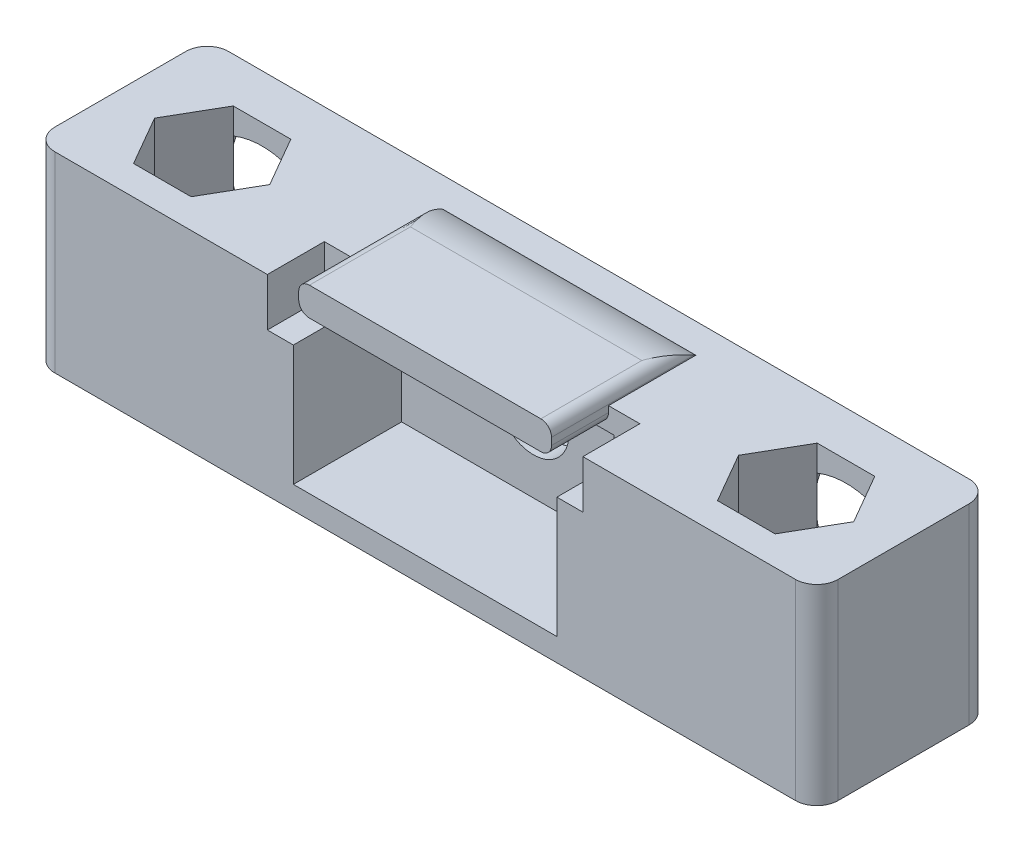
SolidWorks part; units mm, degrees
ref_plane "Front Plane" through (0, 0, 0) normal (0, 0, 1) x (1, 0, 0)
ref_plane "Top Plane" through (0, 0, 0) normal (0, 1, 0) x (1, 0, 0)
ref_plane "Right Plane" through (0, 0, 0) normal (1, 0, 0) x (0, 0, -1)
sketch "Sketch2" plane through (0, 0, 0) normal (0, 0, 1) x (1, 0, 0)
  line L1 (0, 0) -> (55, 0)
  line L2 (0, 0) -> (0, 13.45)
  line L3 (0, 13.45) -> (55, 13.45)
  line L4 (55, 0) -> (55, 13.45)
  dimension "D1" = 13.45
  dimension "D2" = 55
extrude "Boss-Extrude1" add sketch "Sketch2" along normal blind 12.2
sketch "Sketch3" plane through (0, 0, 12.2) normal (0, 0, 1) x (1, 0, 0)
  line L0 (0, 0) -> (55, 0) construction
  line L1 (18.25, 11.85) -> (36.75, 11.85)
  line L2 (18.25, 11.85) -> (18.25, 1.6)
  line L3 (18.25, 1.6) -> (36.75, 1.6)
  line L4 (36.75, 11.85) -> (36.75, 1.6)
  line L5 (27.5, 26.9) -> (27.5, 0) construction
  line L7 (27.5, 0) -> (27.5, -19.69) construction
  point P6 (27.5, 11.85)
  point P9 (27.5, 13.45)
  dimension "D1" = 1.6
  dimension "D2" = 18.5
  dimension "D3" = 11.85
extrude "Cut-Extrude1" cut sketch "Sketch3" against normal blind 7.6
sketch "Sketch5" plane through (0, 0, 12.2) normal (0, 0, 1) x (1, 0, 0)
  line L0 (27.5, 13.45) -> (27.5, -4.8209) construction
  line L1 (55, 13.45) -> (0, 13.45) construction
  line L3 (16.425, 13.45) -> (38.575, 13.45)
  line L4 (16.425, 13.45) -> (16.425, 11.85)
  line L5 (16.425, 11.85) -> (38.575, 11.85)
  line L6 (38.575, 13.45) -> (38.575, 11.85)
  point P1 (27.5, 13.45)
  dimension "D1" = 1.6
  dimension "D2" = 22.15
extrude "Cut-Extrude2" cut sketch "Sketch5" against normal blind 4
sketch "Sketch6" plane through (0, 0, 12.2) normal (0, 0, 1) x (1, 0, 0)
  line L0 (27.5, 0) -> (27.5, 20.3445) construction
  line L1 (0, 0) -> (55, 0) construction
  line L2 (36.75, 11.85) -> (18.25, 11.85) construction
  line L3 (18.625, 12.275) -> (36.375, 12.275)
  line L4 (18.625, 12.275) -> (18.625, 14.275)
  line L5 (18.625, 14.275) -> (36.375, 14.275)
  line L6 (36.375, 12.275) -> (36.375, 14.275)
  point P10 (27.5, 14.275)
  dimension "D1" = 0.425
  dimension "D2" = 17.75
  dimension "D3" = 2
extrude "Boss-Extrude2" add sketch "Sketch6" against normal blind 8.7
sketch "Sketch7" plane through (0, 0, 12.2) normal (0, 0, 1) x (1, 0, 0)
  line L0 (36.75, 1.6) -> (36.75, 11.85) construction
  line L1 (38.575, 13.45) -> (36.75, 13.45)
  line L2 (38.575, 13.45) -> (38.575, 10.075)
  line L3 (38.575, 10.075) -> (36.75, 10.075)
  line L4 (36.75, 13.45) -> (36.75, 10.075)
  line L5 (18.25, 11.85) -> (18.25, 1.6) construction
  line L6 (16.425, 13.45) -> (18.25, 13.45)
  line L7 (16.425, 13.45) -> (16.425, 10.075)
  line L8 (16.425, 10.075) -> (18.25, 10.075)
  line L9 (18.25, 13.45) -> (18.25, 10.075)
  dimension "D1" = 3.375
  dimension "D2" = 3.375
extrude "Cut-Extrude3" cut sketch "Sketch7" against normal up to surface (4 mm away) up to face at (27.5, 12.575, 8.2)
fillet "Fillet1" radius 0.75 2 edges at (36.375, 14.275, 7.85) (36.375, 12.275, 10.2)
fillet "Fillet3" radius 0.75 2 edges at (18.625, 12.275, 10.2) (18.625, 14.275, 7.85)
draft "Draft4" type of draft neutral plane draft angle 60 faces to draft 1 face at (27.5, 13.8018, 3.5) neutral plane through (18.625, 14.275, 3.5) neutral plane normal (0, 1, 0) parameters "D1"=60
fillet "Fillet5" radius 6 3 edges at (27.5, 14.275, 3.5) (36.1553, 14.0553, 3.1195) (18.8447, 14.0553, 3.1195)
sketch "Sketch8" plane through (0, 0, 4.6) normal (0, 0, 1) x (1, 0, 0)
  line L0 (18.25, 6.725) -> (36.75, 6.725) construction
  line L1 (18.25, 11.85) -> (18.25, 1.6) construction
  line L2 (27.5, 1.6) -> (27.5, 11.85) construction
  line L3 (18.25, 1.6) -> (36.75, 1.6) construction
  line L4 (36.75, 11.85) -> (18.25, 11.85) construction
  line L5 (36.75, 1.6) -> (36.75, 11.85) construction
  circle A0 centre (27.5, 6.725) radius 2.5
extrude "Cut-Extrude4" cut sketch "Sketch8" against normal through all
sketch "Sketch9" plane through (0, 0, 0) normal (0, 0, -1) x (-1, 0, 0)
  circle A0 centre (-27.5, 6.725) radius 4.25
extrude "Cut-Extrude5" cut sketch "Sketch9" against normal blind 3
sketch "Sketch10" plane through (0, 0, 0) normal (0, 0, -1) x (-1, 0, 0)
  line L0 (0, 6.725) -> (-55, 6.725) construction
  line L1 (0, 13.45) -> (0, 0) construction
  line L2 (-55, 0) -> (-55, 13.45) construction
  circle A0 centre (-48, 6.725) radius 5.3
  circle A1 centre (-7, 6.725) radius 5.3
  dimension "D1" = 7
  dimension "D2" = 7
extrude "Cut-Extrude6" cut sketch "Sketch10" against normal blind 3.15
sketch "Sketch11" plane through (0, 13.45, 0) normal (0, 1, 0) x (1, 0, 0)
  line L0 (0, -6.65) -> (55, -6.65) construction
  line L1 (9.0207, -3.15) -> (4.9793, -3.15)
  line L2 (4.9793, -3.15) -> (2.9585, -6.65)
  line L3 (2.9585, -6.65) -> (4.9793, -10.15)
  line L4 (4.9793, -10.15) -> (9.0207, -10.15)
  line L5 (9.0207, -10.15) -> (11.0415, -6.65)
  line L6 (11.0415, -6.65) -> (9.0207, -3.15)
  line L9 (27.5, -6.65) -> (27.5, -18.6651) construction
  line L10 (43.9585, -6.65) -> (45.9793, -3.15)
  line L11 (45.9793, -10.15) -> (43.9585, -6.65)
  line L12 (50.0207, -10.15) -> (45.9793, -10.15)
  line L13 (52.0415, -6.65) -> (50.0207, -10.15)
  line L14 (50.0207, -3.15) -> (52.0415, -6.65)
  line L15 (45.9793, -3.15) -> (50.0207, -3.15)
  line L17 (16.425, -12.2) -> (0, -12.2) construction
  circle A0 centre (7, -6.65) radius 3.5 construction
  circle A1 centre (48, -6.65) radius 3.5 construction
  dimension "D1" = 7
  dimension "D2" = 7
  dimension "D3" = 5.55
extrude "Cut-Extrude7" cut sketch "Sketch11" against normal blind 11
fillet "Fillet6" radius 1.5 4 edges at (0, 6.725, 12.2) (0, 6.725, 0) (55, 6.725, 12.2) (55, 6.725, 0)
